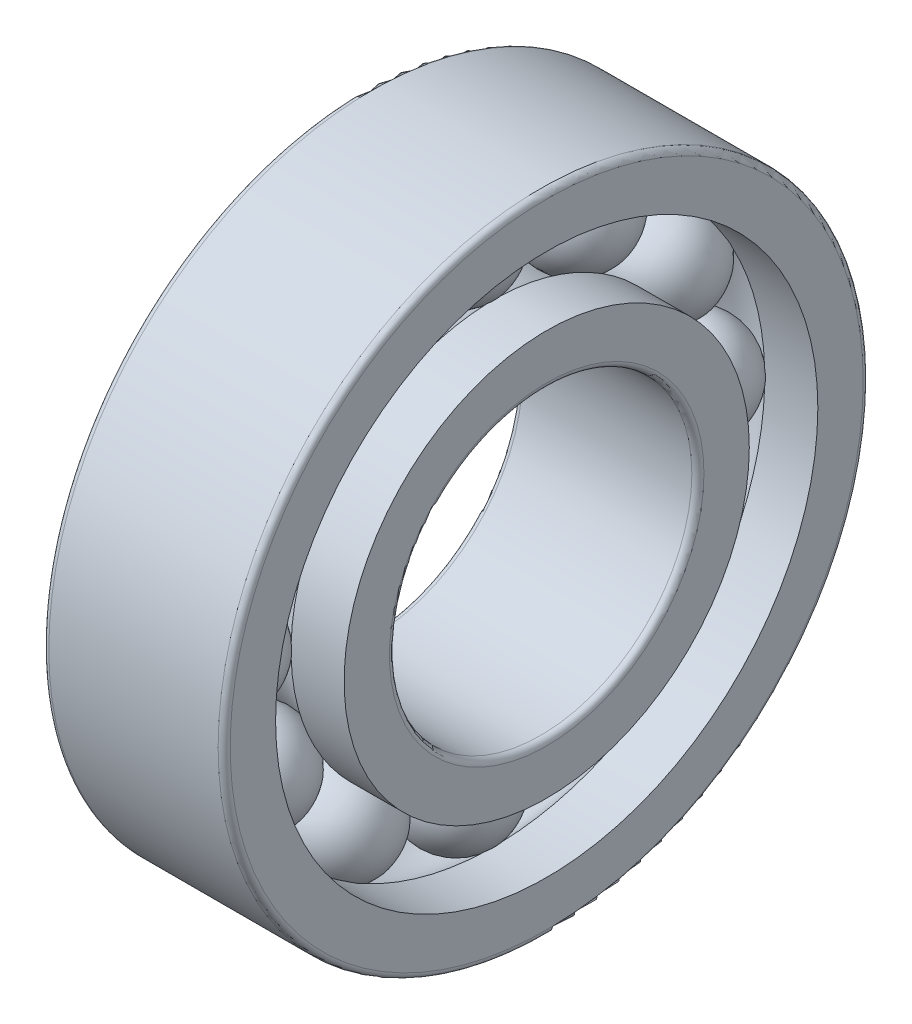
SolidWorks part; units mm, degrees
ref_plane "Plane1" through (0, 0, 0) normal (0, 0, 1) x (1, 0, 0)
ref_plane "Plane2" through (0, 0, 0) normal (0, 1, 0) x (1, 0, 0)
ref_plane "Plane3" through (0, 0, 0) normal (1, 0, 0) x (0, 0, -1)
sketch "Clipboard" plane through (0, 0, 0) normal (0, 0, 1) x (1, 0, 0)
  line L0 (-10, 0) -> (10, 0) construction
  line L1 (0, 0) -> (21.872, -4.649)
  line L2 (0, 0) -> (11.4932, 2.443)
  line L3 (0, 0) -> (21.872, -4.649)
  line L4 (0, 0) -> (-22.3573, -0.3902)
  dimension "BallCLRad" = 11.75
sketch "CagSpiSke" plane through (0, 0, 0) normal (0, 0, 1) x (1, 0, 0)
  line L0 (0.255, 11.325) -> (0.255, 12.175)
  line L1 (0.255, 12.175) -> (-0.255, 12.175)
  line L2 (-0.255, 12.175) -> (-0.255, 11.325)
  line L3 (-0.255, 11.325) -> (0.255, 11.325)
  line L4 (-20.6375, 0) -> (20.6375, 0) construction
  line L5 (0, 0) -> (0, 23.7692) construction
  dimension "OD" = 24.35
  dimension "ID" = 22.65
revolve "CageSpine" add sketch "CagSpiSke" angle 0.001 about L4 reverse direction yes
ref_axis "Axis1" through (-50, 0, 0) along (1, 0, 0)
sketch "CagBalSke" plane through (0, 0, 0) normal (0, 0, 1) x (1, 0, 0)
  line L0 (-2.805, 11.75) -> (2.805, 11.75)
  line L1 (-1.905, 11.75) -> (1.905, 11.75) construction
  line L2 (-10, 0) -> (10, 0) construction
  line L3 (0, 0) -> (0, 24) construction
  arc A0 (2.805, 11.75) -> (-2.805, 11.75) centre (0, 11.75) cw
  dimension "BallCLRad" = 11.75
revolve "CageBall" [suppressed] add sketch "CagBalSke" angle 360 about L1 reverse direction yes
pattern_circular "CageBalls" [suppressed] count 12 every 30 about axis through (-50, 0, 0) along (1, 0, 0)
sketch "CagTrmODSke" plane through (0, 0, 0) normal (0, 0, 1) x (1, 0, 0)
  line L0 (2.806, 12.175) -> (2.806, 14.556)
  line L1 (2.806, 14.556) -> (-2.806, 14.556)
  line L2 (-2.806, 14.556) -> (-2.806, 12.175)
  line L3 (-2.806, 12.175) -> (2.806, 12.175)
  line L4 (-20.6375, 0) -> (20.6375, 0) construction
  line L5 (0, 0) -> (0, 25) construction
  dimension "Width" = 5.612
  dimension "ID" = 24.35
  dimension "OD" = 29.112
revolve "CageTrimOD" [suppressed] cut sketch "CagTrmODSke" angle 360 about L4 reverse direction yes
sketch "CagTrmIDSke" plane through (0, 0, 0) normal (0, 0, 1) x (1, 0, 0)
  line L0 (2.806, 8.946) -> (2.806, 11.325)
  line L1 (2.806, 11.325) -> (-2.806, 11.325)
  line L2 (-2.806, 11.325) -> (-2.806, 8.946)
  line L3 (-2.806, 8.946) -> (2.806, 8.946)
  line L4 (-20.6375, 0) -> (20.6375, 0) construction
  line L5 (0, 0) -> (0, 25) construction
  dimension "Width" = 5.612
  dimension "ID" = 17.892
  dimension "OD" = 22.65
revolve "CageTrimID" [suppressed] cut sketch "CagTrmIDSke" angle 360 about L4 reverse direction yes
sketch "BalSimSke" plane through (0, 0, 0) normal (0, 0, 1) x (1, 0, 0)
  line L0 (-10, 0) -> (10, 0) construction
  line L1 (-10, 11.75) -> (10, 11.75) construction
  line L2 (0, 0) -> (0, 23) construction
  circle A0 centre (0, 11.75) radius 2.55
  dimension "BallCLRad" = 11.75
  dimension "Ball_diameter" = 5.1
revolve "BallsSimplified" [suppressed] add sketch "BalSimSke" angle 360 about L0
sketch "BalDetSke" plane through (0, 0, 0) normal (0, 0, 1) x (1, 0, 0)
  line L0 (-2.55, 11.75) -> (2.55, 11.75)
  line L1 (-1.905, 11.75) -> (1.905, 11.75) construction
  line L2 (0, 0) -> (0, 25) construction
  arc A0 (2.55, 11.75) -> (-2.55, 11.75) centre (0, 11.75) cw
  dimension "BallCLRad" = 11.75
  dimension "Ball_diameter" = 5.1
revolve "BallDetailed" add sketch "BalDetSke" angle 360 about L1 reverse direction yes
sketch "InnRacSke" plane through (0, 0, 0) normal (0, 0, 1) x (1, 0, 0)
  line L0 (-1.867, 10.05) -> (-4.5, 10.05)
  line L1 (-4.5, 10.05) -> (-4.5, 7.8)
  line L2 (-4.2, 7.5) -> (4.2, 7.5)
  line L3 (4.5, 7.8) -> (4.5, 10.05)
  line L4 (4.5, 10.05) -> (1.867, 10.05)
  line L5 (-20.6375, 0) -> (20.6375, 0) construction
  line L6 (0, 0) -> (0, 30) construction
  arc A0 (-4.5, 7.8) -> (-4.2, 7.5) centre (-4.2, 7.8) ccw
  arc A1 (4.2, 7.5) -> (4.5, 7.8) centre (4.2, 7.8) ccw
  arc A2 (1.867, 10.05) -> (-1.867, 10.05) centre (0, 11.75) cw
  dimension "BallCLRad" = 11.75
  dimension "Fillet_radius" = 0.3
  dimension "Ball_diameter" = 5.05
  dimension "ID" = 15
  dimension "OD" = 20.1
  dimension "Width" = 9
revolve "InnerRace" add sketch "InnRacSke" angle 360 about L5 reverse direction yes
sketch "OutRacSke" plane through (0, 0, 0) normal (0, 0, 1) x (1, 0, 0)
  line L0 (-1.867, 13.45) -> (-4.5, 13.45)
  line L1 (-4.5, 13.45) -> (-4.5, 15.7)
  line L2 (-4.2, 16) -> (4.2, 16)
  line L3 (4.5, 15.7) -> (4.5, 13.45)
  line L4 (4.5, 13.45) -> (1.867, 13.45)
  line L5 (-20.6375, 0) -> (20.6375, 0) construction
  line L6 (0, 0) -> (0, 30) construction
  arc A0 (-4.5, 15.7) -> (-4.2, 16) centre (-4.2, 15.7) cw
  arc A1 (4.2, 16) -> (4.5, 15.7) centre (4.2, 15.7) cw
  arc A2 (1.867, 13.45) -> (-1.867, 13.45) centre (0, 11.75) ccw
  dimension "BallCLRad" = 11.75
  dimension "Fillet_radius" = 0.3
  dimension "Ball_diameter" = 5.05
  dimension "Width" = 9
revolve "OuterRace" add sketch "OutRacSke" angle 360 about L5 reverse direction yes
pattern_circular "BallsDetailed" count 12 every 30 about axis through (-50, 0, 0) along (1, 0, 0) of "BallDetailed"
equation "\"BallCLRad@Clipboard\" = ( \"OD@OutRacSke\" + \"ID@InnRacSke\" ) / 4"
equation "\"BallCLRad@BalSimSke\" = \"BallCLRad@Clipboard\""
equation "\"BallCLRad@BalDetSke\" = \"BallCLRad@Clipboard\""
equation "\"BallCLRad@InnRacSke\" = \"BallCLRad@Clipboard\""
equation "\"BallCLRad@OutRacSke\" = \"BallCLRad@Clipboard\""
equation "\"Ball_diameter@InnRacSke\" = \"Ball_diameter@BalDetSke\" - 0.05"
equation "\"Ball_diameter@OutRacSke\" = \"Ball_diameter@BalDetSke\" - 0.05"
equation "\"Ball_diameter@BalSimSke\" = \"Ball_diameter@BalDetSke\""
equation "\"Width@OutRacSke\" = \"Width@InnRacSke\""
equation "\"Fillet_radius@OutRacSke\" = \"Fillet_radius@InnRacSke\""
equation "\"Max_count@Clipboard\" = int( 3.14159265 / atn(( \"Ball_diameter@BalDetSke\" / 2) / sqr( \"BallCLRad@Clipboard\"  *  \"BallCLRad@Clipboard\" - ( \"Ball_diameter@BalDetSke\" / 2) *  ( \"Ball_diameter@BalDetSke\" / 2))))"
equation "\"Max_count@Clipboard\" = ((sgn( \"Max_count@Clipboard\" - \"Count@Clipboard\" )-1)*( \"Max_count@Clipboard\" - \"Count@Clipboard\" ))/-2+ \"Count@Clipboard\""
equation "\"Count@BallsDetailed\" = int( \"Show_count@Clipboard\" ) "
equation "\"Count@BallsDetailed\" = ((sgn( \"Count@BallsDetailed\" - \"Max_count@Clipboard\" )-1)*( \"Count@BallsDetailed\" - \"Max_count@Clipboard\" ))/-2+ \"Max_count@Clipboard\""
equation "\"Count@BallsDetailed\" = ((sgn( \"Count@BallsDetailed\" - \"Min_count@Clipboard\" )+1)*( \"Count@BallsDetailed\" - \"Min_count@Clipboard\"))/2 +\"Min_count@Clipboard\""
equation "\"Angle@BallsDetailed\" = 360.0 / \"Max_count@Clipboard\""
equation "\"BallCLRad@CagBalSke\" = \"BallCLRad@Clipboard\""
equation "\"Count@CageBalls\" = \"Count@BallsDetailed\""
equation "\"Angle@CageBalls\" = \"Angle@BallsDetailed\""
equation "\"Angle@CageSpine\" =  \"Angle@CageBalls\" * ( \"Count@CageBalls\" -1 + int( \"Count@CageBalls\" / \"Max_count@Clipboard\" ) )  + 0.001 -  int( \"Count@CageBalls\" / \"Max_count@Clipboard\" ) * 0.001"
equation "\"Angle@CageSpine\" =  \"Angle@CageSpine\" * int( \"Min_count@Clipboard\" / 2) + int(1 / \"Min_count@Clipboard\")  * 0.001"
equation "\"CageWallOD@CagBalSke\" =  \"Ball_diameter@BalDetSke\" * 1.1"
equation "\"Thickness@CagSpiSke\" =  \"Ball_diameter@BalDetSke\" * 0.1"
equation "\"OD@CagTrmODSke\" = \"BallCLRad@Clipboard\" * 2 + \"CageWallOD@CagBalSke\" + 0.002"
equation "\"ID@CagTrmODSke\" = \"BallCLRad@Clipboard\" * 2 + \"Ball_diameter@BalDetSke\" / 6"
equation "\"OD@CagTrmIDSke\" = \"BallCLRad@Clipboard\" * 2 - \"Ball_diameter@BalDetSke\" / 6"
equation "\"ID@CagTrmIDSke\" = \"BallCLRad@Clipboard\" * 2 - \"CageWallOD@CagBalSke\" + 0.002"
equation "\"OD@CagSpiSke\" = \"ID@CagTrmODSke\""
equation "\"ID@CagSpiSke\" = \"OD@CagTrmIDSke\""
equation "\"Width@CagTrmODSke\" = \"CageWallOD@CagBalSke\" + 0.002"
equation "\"Width@CagTrmIDSke\" = \"CageWallOD@CagBalSke\" + 0.002"
